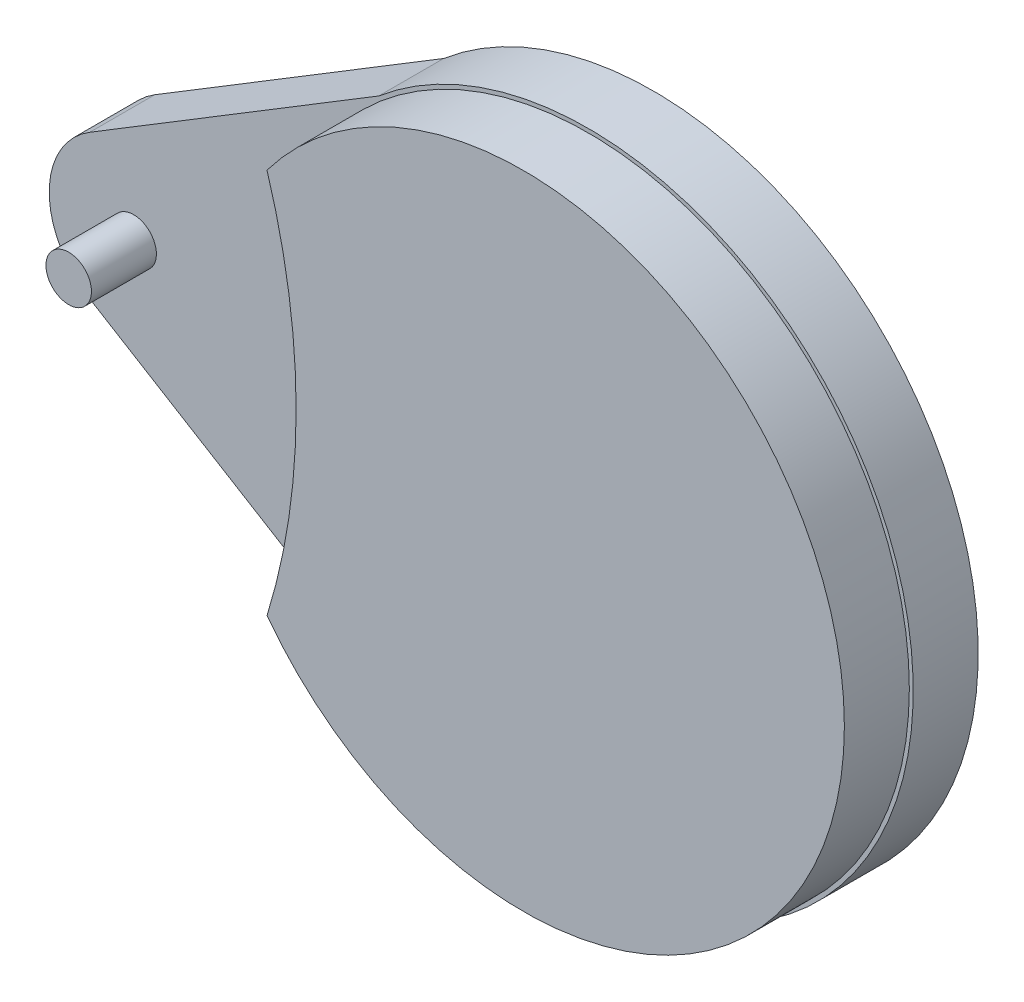
SolidWorks part; units mm, degrees
ref_plane "Front Plane" through (0, 0, 0) normal (0, 0, 1) x (1, 0, 0)
ref_plane "Top Plane" through (0, 0, 0) normal (0, 1, 0) x (1, 0, 0)
ref_plane "Right Plane" through (0, 0, 0) normal (1, 0, 0) x (0, 0, -1)
sketch "Sketch1" plane through (0, 0, 0) normal (0, 0, 1) x (1, 0, 0)
  line L0 (0, 0) -> (43.3013, 25) construction
  line L1 (43.3013, 25) -> (67.7962, 0) construction
  line L2 (67.7962, 0) -> (0, 0) construction
  line L3 (43.3013, 25) -> (28.4023, 16.3981) construction
  line L4 (44.3013, 23.2679) -> (29.4023, 14.666)
  line L5 (42.3013, 26.7321) -> (27.4023, 18.1301)
  line L6 (43.3013, -25) -> (28.4023, -16.3981) construction
  line L7 (42.3013, -26.7321) -> (27.4023, -18.1301)
  line L8 (44.3013, -23.2679) -> (29.4023, -14.666)
  line L9 (0, -50) -> (0, -32.7962) construction
  line L10 (-2, -50) -> (-2, -32.7962)
  line L11 (2, -50) -> (2, -32.7962)
  line L12 (-43.3013, -25) -> (-28.4023, -16.3981) construction
  line L13 (-44.3013, -23.2679) -> (-29.4023, -14.666)
  line L14 (-42.3013, -26.7321) -> (-27.4023, -18.1301)
  line L15 (-43.3013, 25) -> (-28.4023, 16.3981) construction
  line L16 (-42.3013, 26.7321) -> (-27.4023, 18.1301)
  line L17 (-44.3013, 23.2679) -> (-29.4023, 14.666)
  line L18 (0, 50) -> (0, 32.7962) construction
  line L19 (2, 50) -> (2, 32.7962)
  line L20 (-2, 50) -> (-2, 32.7962)
  line L21 (29.4162, 5.5521) -> (54.9522, 21.0979)
  line L22 (29.4162, -5.5521) -> (54.9522, -21.0979)
  circle A0 centre (67.7962, 0) radius 35
  circle A1 centre (0, 0) radius 32.7962 construction
  circle A2 centre (0, 0) radius 50
  arc A3 (44.3013, 23.2679) -> (42.3013, 26.7321) centre (43.3013, 25) ccw
  arc A4 (27.4023, 18.1301) -> (29.4023, 14.666) centre (28.4023, 16.3981) ccw
  circle A5 centre (67.7962, 0) radius 25
  arc A6 (48.0582, 14.8493) -> (48.0582, -14.8493) centre (67.7962, 0) cw
  arc A7 (48.0582, -14.8493) -> (48.0582, 14.8493) centre (0, 0) ccw
  circle A8 centre (33.8981, -58.7132) radius 25
  arc A9 (42.3013, -26.7321) -> (44.3013, -23.2679) centre (43.3013, -25) ccw
  arc A10 (29.4023, -14.666) -> (27.4023, -18.1301) centre (28.4023, -16.3981) ccw
  circle A11 centre (-33.8981, -58.7132) radius 25
  arc A12 (-2, -50) -> (2, -50) centre (0, -50) ccw
  arc A13 (2, -32.7962) -> (-2, -32.7962) centre (0, -32.7962) ccw
  circle A14 centre (-67.7962, 0) radius 25
  arc A15 (-44.3013, -23.2679) -> (-42.3013, -26.7321) centre (-43.3013, -25) ccw
  arc A16 (-27.4023, -18.1301) -> (-29.4023, -14.666) centre (-28.4023, -16.3981) ccw
  circle A17 centre (-33.8981, 58.7132) radius 25
  arc A18 (-42.3013, 26.7321) -> (-44.3013, 23.2679) centre (-43.3013, 25) ccw
  arc A19 (-29.4023, 14.666) -> (-27.4023, 18.1301) centre (-28.4023, 16.3981) ccw
  circle A20 centre (33.8981, 58.7132) radius 25
  arc A21 (2, 50) -> (-2, 50) centre (0, 50) ccw
  arc A22 (-2, 32.7962) -> (2, 32.7962) centre (0, 32.7962) ccw
  circle A23 centre (32.7962, 0) radius 1.75
  circle A24 centre (32.7962, 0) radius 6.5
  point P7 (35.8518, 20.699)
  point P21 (35.8518, -20.699)
  point P30 (0, -41.3981)
  point P39 (-35.8518, -20.699)
  point P48 (-35.8518, 20.699)
  point P57 (0, 41.3981)
  point P64 (0, 0)
  point P70 (0, 0)
  point P71 (63.7697, -25.398)
  point P72 (0, 0)
  dimension "D4" = 2
  dimension "D5" = 50
  dimension "D6" = 0.3
  dimension "D7" = 0.3
  dimension "D8" = 6
  dimension "D9" = 3.5
  dimension "D10" = 13
  dimension "D1" = 50
  dimension "D2" = 35
  dimension "D3" = 30
extrude "Boss-Extrude1" add sketch "Sketch1" against normal blind 5 contours A7 A6 | A2 A5 | A6 A7 L21 A5 A2 L22 | A5 L21 A2 | A24 A0 L22 A2 A5 L21 | A0 A24 A23 | A0 A23 | A0 A23 | A0 A24 A23 | A24 A0 L21 | A24 L22 A0 | A5 A2 L22 | L21 A6 L22 A5 region at (40.832, 0, 0) region at (48.7275, 16.7542, 0) region at (32.5008, 6.9693, 0) region at (78.2914, 22.619, 0) region at (53.3253, 20.0574, 0) region at (46.6418, 0, 0) region at (30.0041, 0, 0) region at (35.8313, 0, 0) region at (69.5024, 0, 0) region at (48.7275, -16.7542, 0) region at (32.5008, -6.9693, 0) region at (33.5467, 0, 0) region at (32.0614, 0, 0)
extrude "Boss-Extrude2" add sketch "Sketch1<4>" along normal blind 5 contours A7 A6 | A0 A23 | A0 A23 region at (69.5024, 0, 0) region at (33.5467, 0, 0) region at (32.0614, 0, 0)
sketch "Sketch1<4>" plane through (0, 0, 0) normal (0, 0, 1) x (1, 0, 0) same geometry as "Sketch1"
